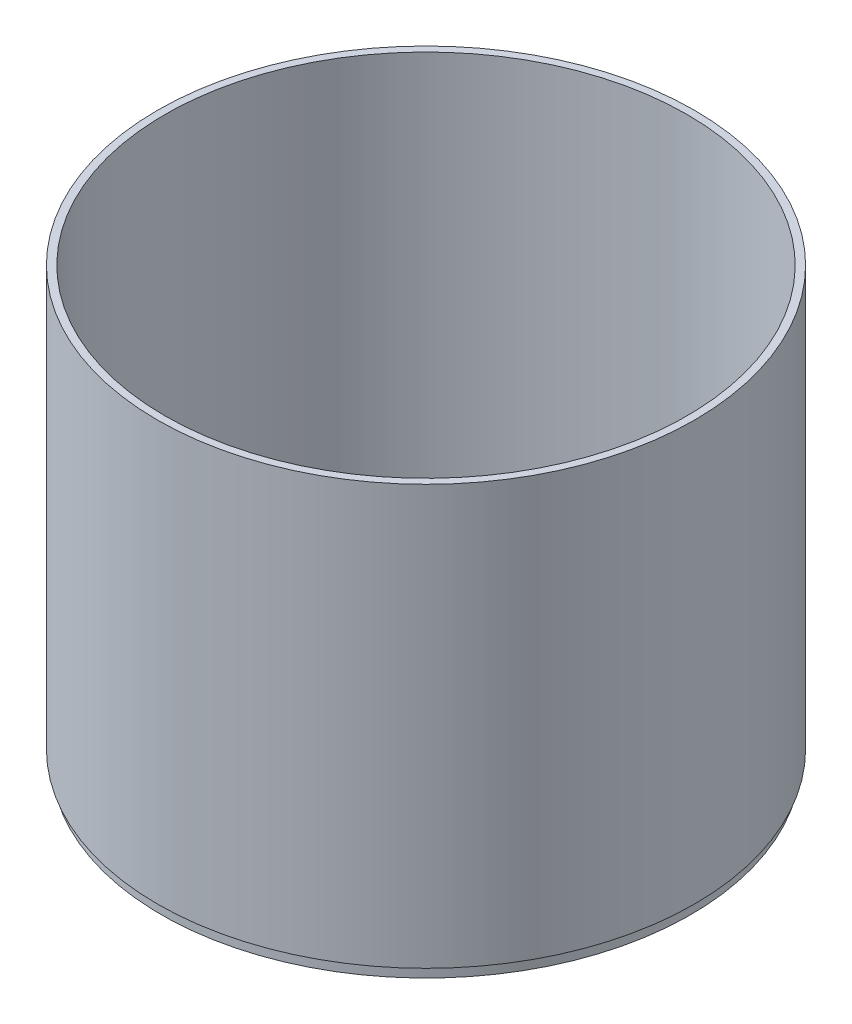
SolidWorks part; units mm, degrees
material "Silica Phenolic"
ref_plane "Piano frontale" through (0, 0, 0) normal (0, 0, 1) x (1, 0, 0)
ref_plane "Piano superiore" through (0, 0, 0) normal (0, 1, 0) x (1, 0, 0)
ref_plane "Piano destro" through (0, 0, 0) normal (1, 0, 0) x (0, 0, -1)
sketch "Schizzo1" plane through (0, 0, 0) normal (0, 0, 1) x (1, 0, 0)
  line L0 (-71, 3) -> (-71, 0)
  line L2 (-73, 3) -> (-73, 117)
  line L3 (-73, 117) -> (-71, 117)
  line L8 (0, 0) -> (0, 47.1479) construction
  line L9 (-71, 0) -> (-72, 0)
  line L10 (-72, 0) -> (-72, 3)
  line L11 (-72, 3) -> (-73, 3)
  line L12 (-71, 3) -> (-71, 117)
  dimension "D1" = 146
  dimension "D3" = 3
  dimension "D4" = 1
  dimension "D5" = 1
  dimension "D6" = 117
revolve "Rivoluzione1" add sketch "Schizzo1" angle 360 about L8 region at (-71.9935, 59.2403, 0)
